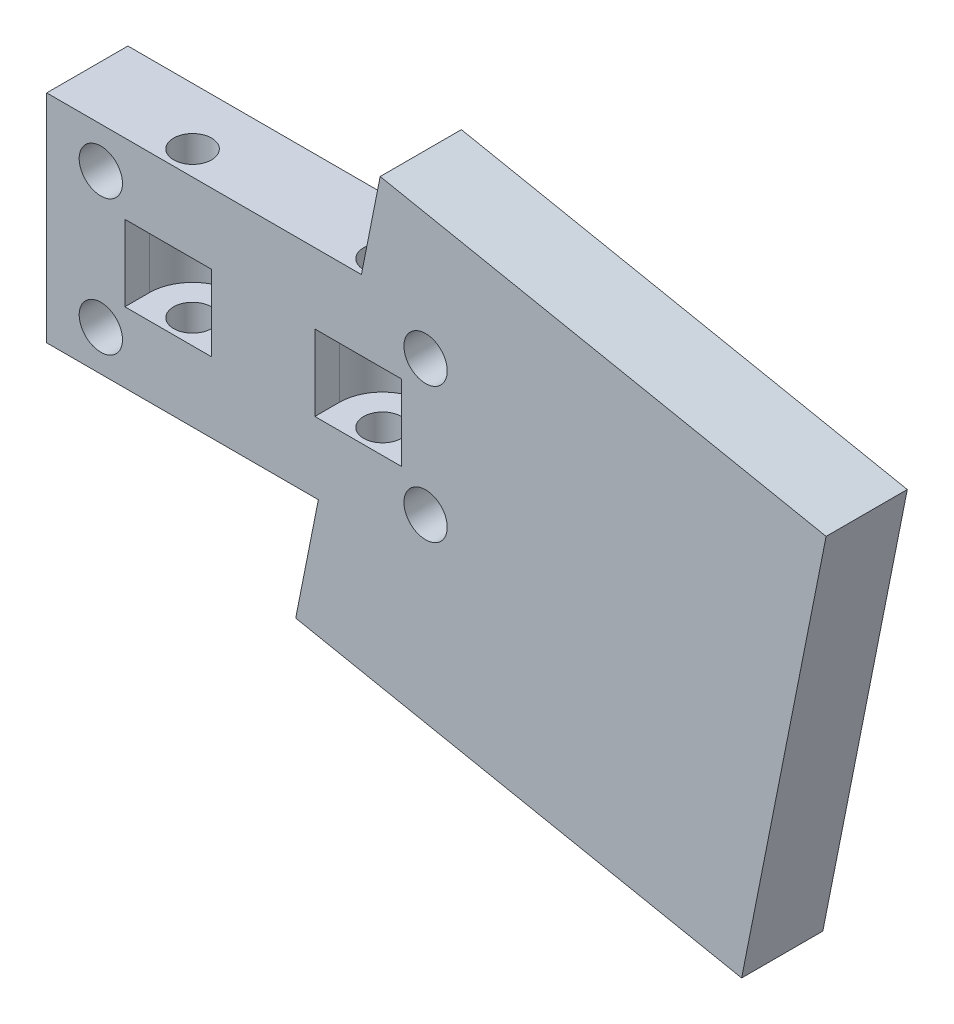
SolidWorks part; units mm, degrees
ref_plane "Front Plane" through (0, 0, 0) normal (0, 0, 1) x (1, 0, 0)
ref_plane "Top Plane" through (0, 0, 0) normal (0, 1, 0) x (1, 0, 0)
ref_plane "Right Plane" through (0, 0, 0) normal (1, 0, 0) x (0, 0, -1)
sketch "Sketch1" plane through (0, 0, 0) normal (0, 0, 1) x (1, 0, 0)
  line L2 (-38.1, -12.7) -> (-38.1, 12.7)
  line L3 (-38.1, 12.7) -> (38.1, 12.7)
  line L10 (38.1, -12.7) -> (38.1, 12.7)
  line L11 (-38.1, -12.7) -> (38.1, -12.7)
  line L14 (-38.1, 12.7) -> (38.1, -12.7) construction
  point P2 (0, 0)
  dimension "D1" = 76.2
  dimension "D2" = 25.4
extrude "Boss-Extrude1" add sketch "Sketch1" along normal blind 9.525
sketch "Sketch6" plane through (0, 0, 9.525) normal (0, 0, -1) x (-1, 0, 0)
  line L4 (8.8878, -26.0589) -> (-43.4272, -36.465)
  line L6 (8.8878, -26.0589) -> (-1.0228, 23.765)
  line L23 (-43.4272, -36.465) -> (-53.3378, 13.3589)
  line L24 (-1.0228, 23.765) -> (-53.3378, 13.3589)
  line L25 (8.8878, -26.0589) -> (-53.3378, 13.3589) construction
  line L26 (-43.4272, -36.465) -> (-1.0228, 23.765) construction
  line L27 (-38.1, 12.7) -> (38.1, 12.7) construction
  point P1 (-22.225, -6.35)
  dimension "D1" = 53.34
  dimension "D2" = 50.8
  dimension "D3" = 11.25
  dimension "D4" = 6.35
  dimension "D5" = 22.225
extrude "Boss-Extrude2" add sketch "Sketch6" along normal up to surface (9.525 mm away) up to face at (0, 0, 0)
sketch "Sketch4" plane through (0, 0, 0) normal (0, 1, 0) x (1, 0, 0)
  line L7 (-1.1782, -9.525) -> (-38.1, -9.525) construction
  line L8 (-28.9242, -6.6675) -> (-28.9242, -9.525)
  line L9 (-18.7643, -6.6675) -> (-18.7642, -9.525)
  line L10 (-18.7642, -9.525) -> (-28.9242, -9.525)
  line L11 (-38.1, -9.525) -> (-38.1, 0) construction
  arc A2 (-18.7643, -6.6675) -> (-28.9242, -6.6675) centre (-23.8442, -6.6675) ccw
  dimension "D1" = 10.16
  dimension "D2" = 2.8575
  dimension "D3" = 14.2558
extrude "Cut-Extrude2" cut sketch "Sketch4" against normal mid plane 8.89
ref_plane "Plane3" through (-12.7, 0, 0) normal (-1, 0, 0) x (0, 0, 1)
sketch "Sketch2" plane through (0, 0, 9.525) normal (0, 0, 1) x (1, 0, 0)
  line L0 (-38.1, -12.7) -> (-6.2306, -12.7) construction
  line L1 (-38.1, 12.7) -> (-38.1, -12.7) construction
  circle A0 centre (-31.75, 7.9375) radius 2.54
  dimension "D1" = 5.08
  dimension "D2" = 20.6375
  dimension "D3" = 6.35
extrude "Cut-Extrude1" cut sketch "Sketch2" against normal up to surface (9.525 mm away) up to face at (0.6614, -3.175, 0)
sketch "Sketch5" plane through (0, 12.7, 0) normal (0, 1, 0) x (1, 0, 0)
  line L0 (-1.1782, -9.525) -> (-38.1, -9.525) construction
  line L1 (-38.1, -9.525) -> (-38.1, 0) construction
  circle A0 centre (-23.8442, -6.6675) radius 2.2225
  dimension "D3" = 4.445
  dimension "D1" = 2.8575
  dimension "D2" = 14.2558
extrude "Cut-Extrude3" cut sketch "Sketch5" along normal blind 3.175 and the other way through all
mirror "Mirror1" about plane through (0, 0, 0) normal (0, 1, 0) of "Cut-Extrude1"
mirror "Mirror2" about plane through (-12.7, 0, 0) normal (-1, 0, 0) of "Mirror1", "Cut-Extrude3", "Cut-Extrude2"
